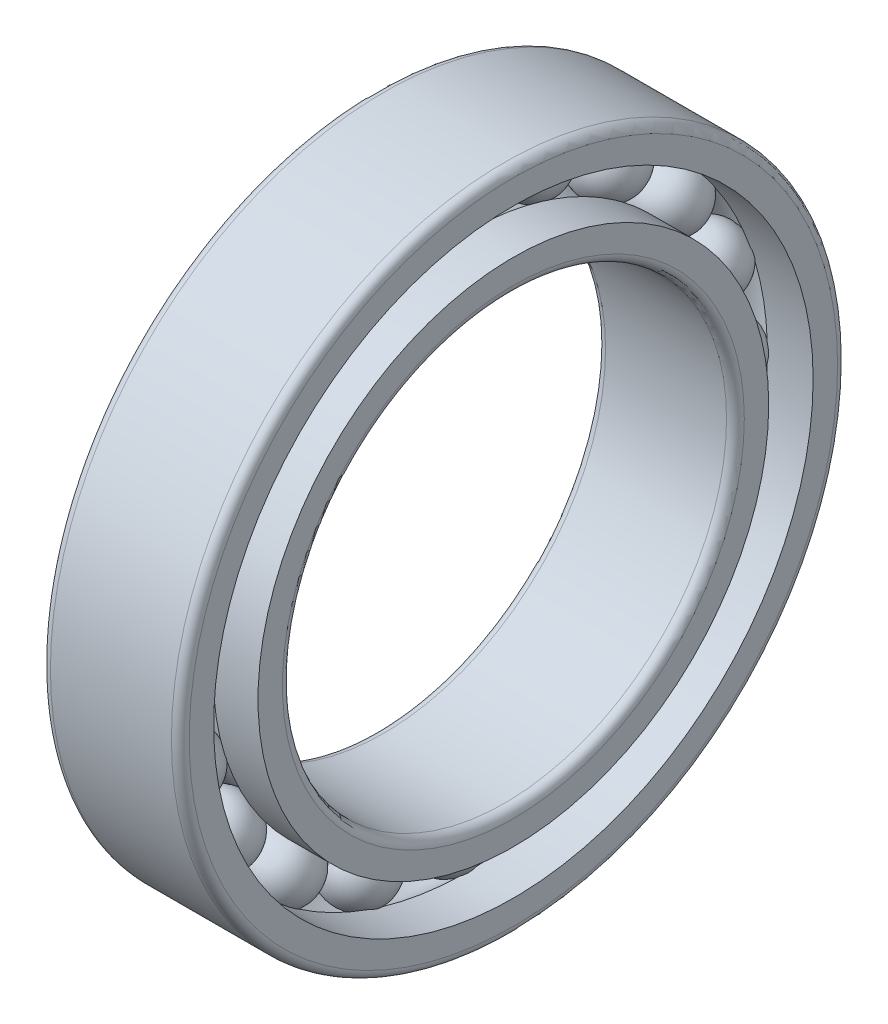
SolidWorks part; units mm, degrees
ref_plane "Plane1" through (0, 0, 0) normal (0, 0, 1) x (1, 0, 0)
ref_plane "Plane2" through (0, 0, 0) normal (0, 1, 0) x (1, 0, 0)
ref_plane "Plane3" through (0, 0, 0) normal (1, 0, 0) x (0, 0, -1)
sketch "Clipboard" plane through (0, 0, 0) normal (0, 0, 1) x (1, 0, 0)
  line L0 (-10, 0) -> (10, 0) construction
  line L1 (0, 0) -> (21.0122, -7.6478)
  line L2 (0, 0) -> (7.4588, 2.7148)
  line L3 (0, 0) -> (21.0122, -7.6478)
  line L4 (0, 0) -> (-22.3573, -0.3902)
  dimension "BallCLRad" = 7.9375
  dimension "Count" = 20
  dimension "Show_count" = 20
  dimension "Max_count" = 20
  dimension "Min_count" = 1
sketch "CagSpiSke" plane through (0, 0, 0) normal (0, 0, 1) x (1, 0, 0)
  line L0 (0.0952, 7.7787) -> (0.0953, 8.0962)
  line L1 (0.0953, 8.0962) -> (-0.0953, 8.0962)
  line L2 (-0.0953, 8.0962) -> (-0.0952, 7.7787)
  line L3 (-0.0952, 7.7787) -> (0.0952, 7.7787)
  line L4 (-20.6375, 0) -> (20.6375, 0) construction
  line L5 (0, 0) -> (0, 23.7692) construction
  dimension "Thickness" = 0.1905
  dimension "OD" = 16.1925
  dimension "ID" = 15.5575
revolve "CageSpine" add sketch "CagSpiSke" angle 0.001 about L4 reverse direction yes
ref_axis "Axis1" through (-50, 0, 0) along (1, 0, 0)
sketch "CagBalSke" plane through (0, 0, 0) normal (0, 0, 1) x (1, 0, 0)
  line L0 (-1.0478, 7.9375) -> (1.0478, 7.9375)
  line L1 (-1.905, 7.9375) -> (1.905, 7.9375) construction
  line L2 (-10, 0) -> (10, 0) construction
  line L3 (0, 0) -> (0, 24) construction
  arc A0 (1.0478, 7.9375) -> (-1.0478, 7.9375) centre (0, 7.9375) cw
  dimension "CageWallOD" = 2.0955
  dimension "BallCLRad" = 7.9375
revolve "CageBall" [suppressed] add sketch "CagBalSke" angle 360 about L1 reverse direction yes
pattern_circular "CageBalls" [suppressed] count 20 every 18 about axis through (-50, 0, 0) along (1, 0, 0)
sketch "CagTrmODSke" plane through (0, 0, 0) normal (0, 0, 1) x (1, 0, 0)
  line L0 (1.0732, 8.0962) -> (1.0732, 9.0107)
  line L1 (1.0732, 9.0107) -> (-1.0732, 9.0107)
  line L2 (-1.0732, 9.0107) -> (-1.0732, 8.0962)
  line L3 (-1.0732, 8.0962) -> (1.0732, 8.0962)
  line L4 (-20.6375, 0) -> (20.6375, 0) construction
  line L5 (0, 0) -> (0, 25) construction
  dimension "Width" = 2.1463
  dimension "ID" = 16.1925
  dimension "OD" = 18.0213
revolve "CageTrimOD" [suppressed] cut sketch "CagTrmODSke" angle 360 about L4 reverse direction yes
sketch "CagTrmIDSke" plane through (0, 0, 0) normal (0, 0, 1) x (1, 0, 0)
  line L0 (1.0732, 6.9151) -> (1.0732, 7.7787)
  line L1 (1.0732, 7.7787) -> (-1.0732, 7.7787)
  line L2 (-1.0732, 7.7787) -> (-1.0732, 6.9151)
  line L3 (-1.0732, 6.9151) -> (1.0732, 6.9151)
  line L4 (-20.6375, 0) -> (20.6375, 0) construction
  line L5 (0, 0) -> (0, 25) construction
  dimension "ID" = 13.8303
  dimension "OD" = 15.5575
  dimension "Width" = 2.1463
revolve "CageTrimID" [suppressed] cut sketch "CagTrmIDSke" angle 360 about L4 reverse direction yes
sketch "BalSimSke" plane through (0, 0, 0) normal (0, 0, 1) x (1, 0, 0)
  line L0 (-10, 0) -> (10, 0) construction
  line L1 (-10, 7.9375) -> (10, 7.9375) construction
  line L2 (0, 0) -> (0, 23) construction
  circle A0 centre (0, 7.9375) radius 0.9525
  dimension "Ball_diameter" = 1.905
  dimension "BallCLRad" = 7.9375
revolve "BallsSimplified" [suppressed] add sketch "BalSimSke" angle 360 about L0
sketch "BalDetSke" plane through (0, 0, 0) normal (0, 0, 1) x (1, 0, 0)
  line L0 (-0.9525, 7.9375) -> (0.9525, 7.9375)
  line L1 (-1.905, 7.9375) -> (1.905, 7.9375) construction
  line L2 (0, 0) -> (0, 25) construction
  arc A0 (0.9525, 7.9375) -> (-0.9525, 7.9375) centre (0, 7.9375) cw
  dimension "Ball_diameter" = 1.905
  dimension "BallCLRad" = 7.9375
revolve "BallDetailed" add sketch "BalDetSke" angle 360 about L1 reverse direction yes
sketch "InnRacSke" plane through (0, 0, 0) normal (0, 0, 1) x (1, 0, 0)
  line L0 (-0.6501, 7.3025) -> (-1.9837, 7.3025)
  line L1 (-1.9837, 7.3025) -> (-1.9837, 6.604)
  line L2 (-1.7297, 6.35) -> (1.7297, 6.35)
  line L3 (1.9837, 6.604) -> (1.9837, 7.3025)
  line L4 (1.9837, 7.3025) -> (0.7009, 7.3025)
  line L5 (-20.6375, 0) -> (20.6375, 0) construction
  line L6 (0, 0) -> (0, 30) construction
  arc A0 (-1.9837, 6.604) -> (-1.7297, 6.35) centre (-1.7297, 6.604) ccw
  arc A1 (1.7297, 6.35) -> (1.9837, 6.604) centre (1.7297, 6.604) ccw
  arc A2 (0.7009, 7.3025) -> (-0.6501, 7.3025) centre (0.0254, 7.9375) cw
  dimension "Fillet_radius" = 0.254
  dimension "Ball_diameter" = 1.8542
  dimension "ID" = 12.7
  dimension "OD" = 14.605
  dimension "Width" = 3.9675
  dimension "BallCLRad" = 7.9375
  dimension "Skew" = 0.0254
revolve "InnerRace" add sketch "InnRacSke" angle 360 about L5 reverse direction yes
sketch "OutRacSke" plane through (0, 0, 0) normal (0, 0, 1) x (1, 0, 0)
  line L0 (-0.6755, 8.5725) -> (-1.9837, 8.5725)
  line L1 (-1.9837, 8.5725) -> (-1.9837, 9.271)
  line L2 (-1.7297, 9.525) -> (1.7297, 9.525)
  line L3 (1.9837, 9.271) -> (1.9837, 8.5725)
  line L4 (1.9837, 8.5725) -> (0.6755, 8.5725)
  line L5 (-20.6375, 0) -> (20.6375, 0) construction
  line L6 (0, 0) -> (0, 30) construction
  arc A0 (-1.9837, 9.271) -> (-1.7297, 9.525) centre (-1.7297, 9.271) cw
  arc A1 (1.7297, 9.525) -> (1.9837, 9.271) centre (1.7297, 9.271) cw
  arc A2 (0.6755, 8.5725) -> (-0.6755, 8.5725) centre (0, 7.9375) ccw
  dimension "Fillet_radius" = 0.254
  dimension "Ball_diameter" = 1.8542
  dimension "OD" = 19.05
  dimension "ID" = 17.145
  dimension "Width" = 3.9675
  dimension "BallCLRad" = 7.9375
revolve "OuterRace" add sketch "OutRacSke" angle 360 about L5 reverse direction yes
pattern_circular "BallsDetailed" count 20 every 18 about axis through (-50, 0, 0) along (1, 0, 0) of "BallDetailed"
equation "\"BallCLRad@Clipboard\" = ( \"OD@OutRacSke\" + \"ID@InnRacSke\" ) / 4"
equation "\"BallCLRad@BalSimSke\" = \"BallCLRad@Clipboard\""
equation "\"BallCLRad@BalDetSke\" = \"BallCLRad@Clipboard\""
equation "\"BallCLRad@InnRacSke\" = \"BallCLRad@Clipboard\""
equation "\"BallCLRad@OutRacSke\" = \"BallCLRad@Clipboard\""
equation "\"Ball_diameter@InnRacSke\" = \"Ball_diameter@BalDetSke\" - 0.002"
equation "\"Ball_diameter@OutRacSke\" = \"Ball_diameter@BalDetSke\" - 0.002"
equation "\"Ball_diameter@BalSimSke\" = \"Ball_diameter@BalDetSke\""
equation "\"Width@OutRacSke\" = \"Width@InnRacSke\""
equation "\"Fillet_radius@OutRacSke\" = \"Fillet_radius@InnRacSke\""
equation "\"Max_count@Clipboard\" = int( 3.14159265 / atn(( \"Ball_diameter@BalDetSke\" / 2) / sqr( \"BallCLRad@Clipboard\"  *  \"BallCLRad@Clipboard\" - ( \"Ball_diameter@BalDetSke\" / 2) *  ( \"Ball_diameter@BalDetSke\" / 2))))"
equation "\"Max_count@Clipboard\" = ((sgn( \"Max_count@Clipboard\" - \"Count@Clipboard\" )-1)*( \"Max_count@Clipboard\" - \"Count@Clipboard\" ))/-2+ \"Count@Clipboard\""
equation "\"Count@BallsDetailed\" = int( \"Show_count@Clipboard\" ) "
equation "\"Count@BallsDetailed\" = ((sgn( \"Count@BallsDetailed\" - \"Max_count@Clipboard\" )-1)*( \"Count@BallsDetailed\" - \"Max_count@Clipboard\" ))/-2+ \"Max_count@Clipboard\""
equation "\"Count@BallsDetailed\" = ((sgn( \"Count@BallsDetailed\" - \"Min_count@Clipboard\" )+1)*( \"Count@BallsDetailed\" - \"Min_count@Clipboard\"))/2 +\"Min_count@Clipboard\""
equation "\"Angle@BallsDetailed\" = 360.0 / \"Max_count@Clipboard\""
equation "\"BallCLRad@CagBalSke\" = \"BallCLRad@Clipboard\""
equation "\"Count@CageBalls\" = \"Count@BallsDetailed\""
equation "\"Angle@CageBalls\" = \"Angle@BallsDetailed\""
equation "\"Angle@CageSpine\" =  \"Angle@CageBalls\" * ( \"Count@CageBalls\" -1 + int( \"Count@CageBalls\" / \"Max_count@Clipboard\" ) )  + 0.001 -  int( \"Count@CageBalls\" / \"Max_count@Clipboard\" ) * 0.001"
equation "\"Angle@CageSpine\" =  \"Angle@CageSpine\" * int( \"Min_count@Clipboard\" / 2) + int(1 / \"Min_count@Clipboard\")  * 0.001"
equation "\"CageWallOD@CagBalSke\" =  \"Ball_diameter@BalDetSke\" * 1.1"
equation "\"Thickness@CagSpiSke\" =  \"Ball_diameter@BalDetSke\" * 0.1"
equation "\"OD@CagTrmODSke\" = \"BallCLRad@Clipboard\" * 2 + \"CageWallOD@CagBalSke\" + 0.002"
equation "\"ID@CagTrmODSke\" = \"BallCLRad@Clipboard\" * 2 + \"Ball_diameter@BalDetSke\" / 6"
equation "\"OD@CagTrmIDSke\" = \"BallCLRad@Clipboard\" * 2 - \"Ball_diameter@BalDetSke\" / 6"
equation "\"ID@CagTrmIDSke\" = \"BallCLRad@Clipboard\" * 2 - \"CageWallOD@CagBalSke\" + 0.002"
equation "\"OD@CagSpiSke\" = \"ID@CagTrmODSke\""
equation "\"ID@CagSpiSke\" = \"OD@CagTrmIDSke\""
equation "\"Width@CagTrmODSke\" = \"CageWallOD@CagBalSke\" + 0.002"
equation "\"Width@CagTrmIDSke\" = \"CageWallOD@CagBalSke\" + 0.002"
